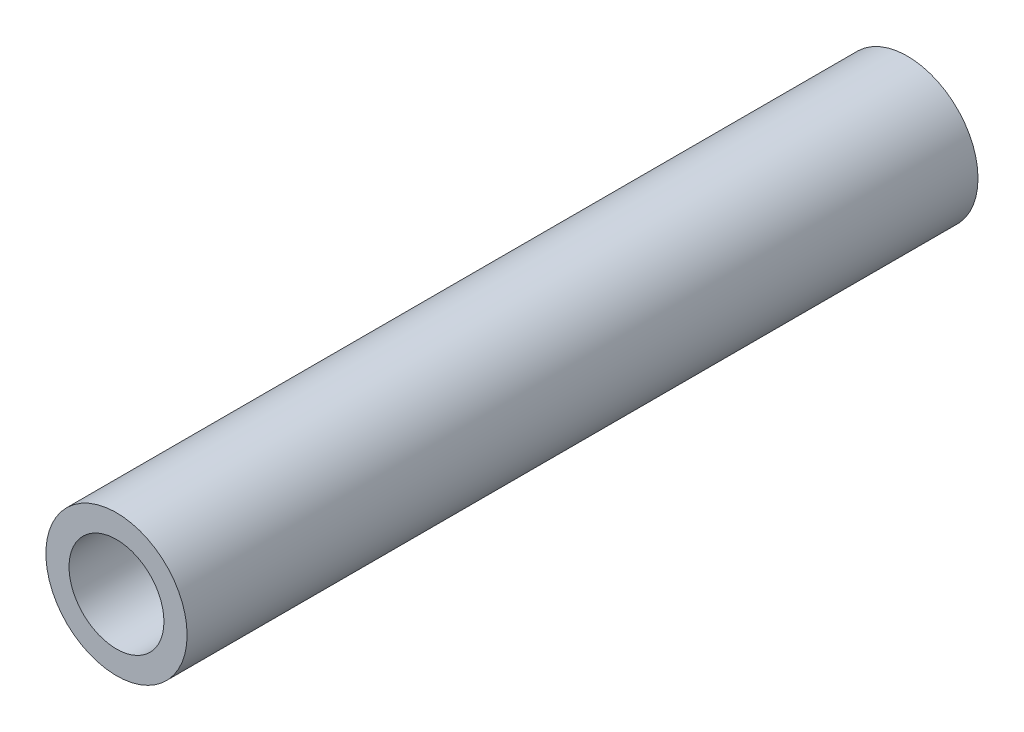
SolidWorks part; units mm, degrees
ref_plane "Спереди" through (0, 0, 0) normal (0, 0, 1) x (1, 0, 0)
ref_plane "Сверху" through (0, 0, 0) normal (0, 1, 0) x (1, 0, 0)
ref_plane "Справа" through (0, 0, 0) normal (1, 0, 0) x (0, 0, -1)
sketch "Эскиз1" plane through (0, 0, 0) normal (0, 0, 1) x (1, 0, 0)
  circle A0 centre (0, 0) radius 4.2
  circle A1 centre (0, 0) radius 6.25
extrude "Бобышка-Вытянуть1" add sketch "Эскиз1" along normal blind 70
